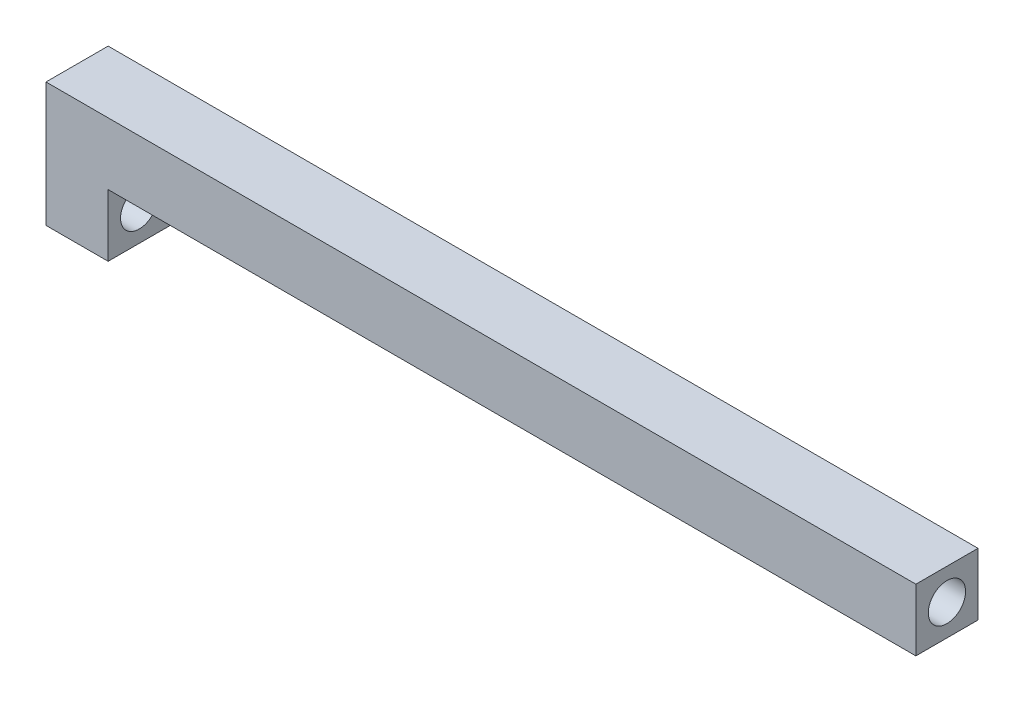
SolidWorks part; units mm, degrees
ref_plane "Front Plane" through (0, 0, 0) normal (0, 0, 1) x (1, 0, 0)
ref_plane "Top Plane" through (0, 0, 0) normal (0, 1, 0) x (1, 0, 0)
ref_plane "Right Plane" through (0, 0, 0) normal (1, 0, 0) x (0, 0, -1)
sketch "Sketch1" plane through (0, 0, 0) normal (0, 0, 1) x (1, 0, 0)
  line L1 (-140, 10) -> (0, 10)
  line L2 (-140, 10) -> (-140, -10)
  line L3 (-140, -10) -> (-130, -10)
  line L5 (-130, 0) -> (-130, -10)
  line L6 (0, 10) -> (0, -10) construction
  line L10 (0, 10) -> (0, 0)
  line L11 (-130, 0) -> (0, 0)
  point P0 (0, 0)
  point P13 (0, 0)
  dimension "D1" = 10
  dimension "D2" = 20
  dimension "D3" = 140
extrude "Boss-Extrude1" add sketch "Sketch1" along normal blind 10
sketch "Sketch4" plane through (0, 0, 0) normal (1, 0, 0) x (0, 0, -1)
  line L0 (-5, 10) -> (-5, -10) construction
  line L1 (-10, 10) -> (0, 10) construction
  line L2 (-10, -10) -> (0, -10) construction
  line L3 (-13.6296, 5) -> (2.2432, 5) construction
  line L4 (-16.8551, -5) -> (3.6579, -5) construction
  circle A0 centre (-5, 5) radius 3
  circle A1 centre (-5, -5) radius 3
  dimension "D3" = 6
  dimension "D4" = 6
  dimension "D1" = 5
  dimension "D2" = 10
extrude "Cut-Extrude2" cut sketch "Sketch4" against normal blind 150 contours A1
extrude "Cut-Extrude3" cut sketch "Sketch4<3>" against normal blind 20 contours A0
sketch "Sketch4<3>" plane through (0, 0, 0) normal (1, 0, 0) x (0, 0, -1) same geometry as "Sketch4"
